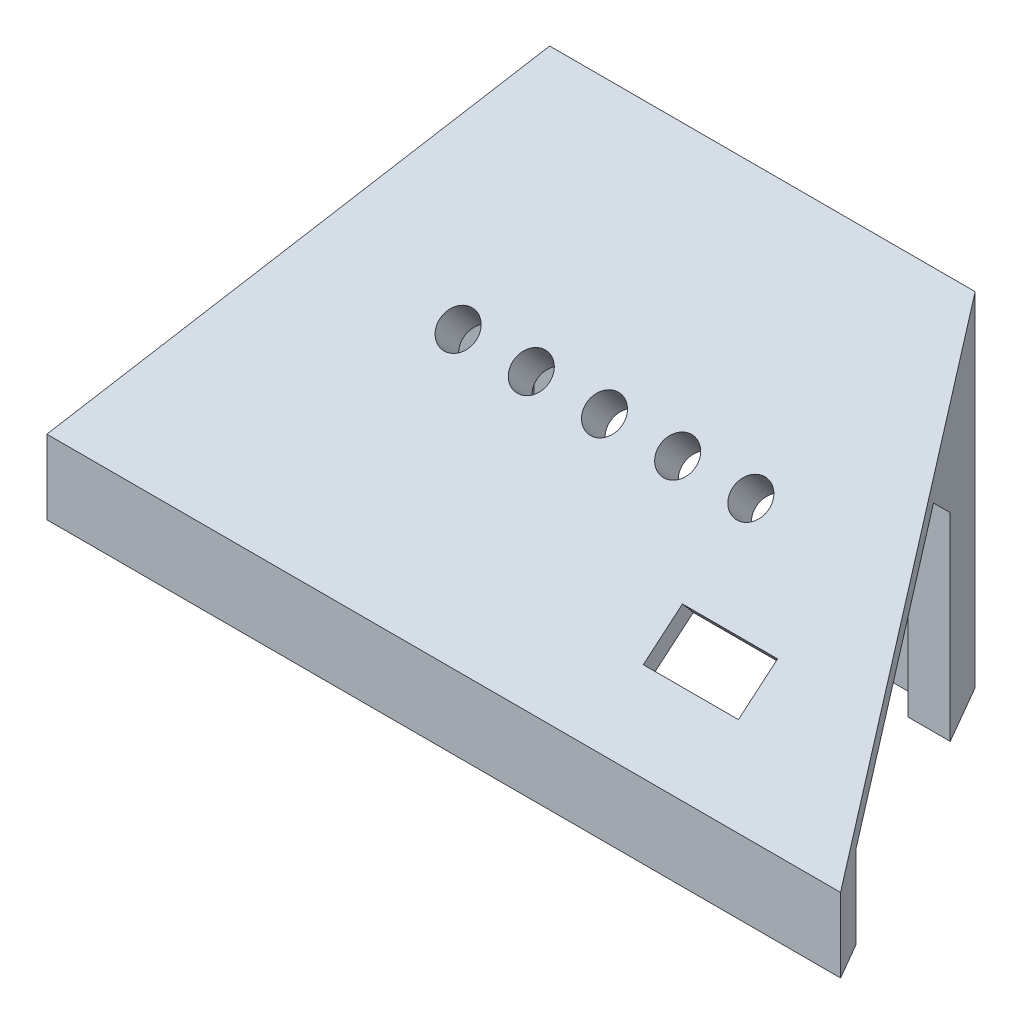
SolidWorks part; units mm, degrees
note: '?' marks a value the reader was unsure of.
other "Markup1"
sketch "Sketch17"
other "Markup2"
sketch "Sketch18"
ref_plane "Front Plane" through (0, 0, 0) normal (0, 0, 1) x (1, 0, 0)
ref_plane "Top Plane" through (0, 0, 0) normal (0, 1, 0) x (1, 0, 0)
ref_plane "Right Plane" through (0, 0, 0) normal (1, 0, 0) x (0, 0, -1)
sketch "Sketch1" plane through (0, 0, 0) normal (0, 1, 0) x (1, 0, 0)
  line L0 (0, 0) -> (108.46, 0)
  line L1 (54.23, 0) -> (54.23, 49.682) construction
  line L2 (25.16, 43.55) -> (83.3, 43.55)
  line L3 (0, 0) -> (25.16, 43.55)
  line L4 (83.3, 43.55) -> (108.46, 0)
  point P8 (54.23, 43.55)
  dimension "D1" = 108.46
  dimension "D2" = 58.14
  dimension "D3" = 43.55
extrude "Boss-Extrude1" add sketch "Sketch1" along normal blind 10.13
sketch "Sketch4" plane through (0, 10.13, 0) normal (0, 1, 0) x (1, 0, 0)
  line L4 (25.16, 43.55) -> (0, 0)
  line L5 (0, 0) -> (108.46, 0)
  line L6 (108.46, 0) -> (83.3, 43.55)
  line L7 (83.3, 43.55) -> (25.16, 43.55)
  line L8 (25.16, 43.55) -> (0, 0)
  line L9 (0, 0) -> (108.46, 0)
  line L10 (108.46, 0) -> (83.3, 43.55)
  line L11 (83.3, 43.55) -> (25.16, 43.55)
  dimension "D1" = 0
extrude "Boss-Extrude2" add sketch "Sketch4" along normal blind 36.74
chamfer "Chamfer1" distance 36.74 distance2 43.55 1 edges at (54.23, 46.87, 0)
sketch "Sketch10" plane through (0, 0, 0) normal (0, -1, 0) x (1, 0, 0)
  line L8 (8.6631, -5) -> (28.0458, -38.55)
  line L9 (28.0458, -38.55) -> (80.4142, -38.55)
  line L10 (80.4142, -38.55) -> (99.7969, -5)
  line L11 (99.7969, -5) -> (8.6631, -5)
  line L12 (8.6631, -5) -> (28.0458, -38.55)
  line L13 (28.0458, -38.55) -> (80.4142, -38.55)
  line L14 (80.4142, -38.55) -> (99.7969, -5)
  line L15 (99.7969, -5) -> (8.6631, -5)
  dimension "D1" = 5
extrude "Cut-Extrude1" cut sketch "Sketch10" against normal blind 50
sketch "Sketch11" plane through (0, 5.9181, 4.9926) normal (0, 0.7643, 0.6448) x (1, 0, 0)
  line L0 (8.6631, 13.0736) -> (99.7969, 13.0736) construction
  line L1 (99.7969, 13.0736) -> (80.4142, 56.9678) construction
  line L2 (80.4142, 56.9678) -> (28.0458, 56.9678) construction
  line L3 (28.0458, 56.9678) -> (8.6631, 13.0736) construction
  line L4 (8.6631, 13.0736) -> (99.7969, 13.0736)
  line L5 (99.7969, 13.0736) -> (80.4142, 56.9678)
  line L6 (80.4142, 56.9678) -> (28.0458, 56.9678)
  line L7 (28.0458, 56.9678) -> (8.6631, 13.0736)
ref_axis "Axis1" through (28.0458, 42.6519, -38.55) along (0, -1, 0)?
extrude "Boss-Extrude3" add sketch "Sketch11" along direction (0, -1, 0) on the side against the normal blind 3
sketch "Sketch12" plane through (0, 0, -43.55) normal (0, 0, -1) x (-1, 0, 0)
  line L0 (-83.3, 0) -> (-25.16, 0) construction
  line L1 (-32.36, 0) -> (-76.1, 0)
  line L2 (-32.36, 0) -> (-32.36, 39.6519)
  line L3 (-32.36, 39.6519) -> (-76.1, 39.6519)
  line L4 (-76.1, 0) -> (-76.1, 39.6519)
  line L5 (-25.16, 46.87) -> (-25.16, 0) construction
  line L6 (-83.3, 46.87) -> (-83.3, 0) construction
  line L7 (-80.4142, 39.6519) -> (-28.0458, 39.6519) construction
  dimension "D1" = 7.2
  dimension "D2" = 7.2
extrude "Cut-Extrude2" cut sketch "Sketch12" against normal up to vertex (5 mm away)
sketch "Sketch13" plane through (0, 5.9181, 4.9926) normal (0, 0.7643, 0.6448) x (1, 0, 0)
  line L0 (54.23, 63.5094) -> (54.23, 6.532) construction
  line L1 (83.3, 63.5094) -> (25.16, 63.5094) construction
  line L2 (108.46, 6.532) -> (0, 6.532) construction
  circle A0 centre (74.23, 35.2749) radius 2.5
  dimension "D1" = 5
  dimension "D2" = 20
extrude "Cut-Extrude3" cut sketch "Sketch13" against normal up to next
sketch "Sketch15" plane through (0, 5.9181, 4.9926) normal (0, 0.7643, 0.6448) x (1, 0, 0)
  circle A0 centre (74.23, 35.2749) radius 2.5 construction
  circle A1 centre (74.23, 35.2749) radius 2.5
  circle A2 centre (74.23, 35.2749) radius 3.5
  dimension "D1" = 1
extrude "Boss-Extrude4" add sketch "Sketch15" against normal blind 5
sketch "Sketch16" plane through (0, 5.9181, 4.9926) normal (0, 0.7643, 0.6448) x (1, 0, 0)
  line L5 (74.1954, 23.0907) -> (87.1954, 23.0907)
  line L6 (74.1954, 23.0907) -> (74.1954, 16.0907)
  line L7 (74.1954, 16.0907) -> (87.1954, 16.0907)
  line L8 (87.1954, 23.0907) -> (87.1954, 16.0907)
  point P1 (0, 0)
  point P6 (87.1954, 16.0907)
  point P11 (74.1954, 23.0907)
  point P14 (74.1954, 16.0907)
  dimension "D1" = 7
  dimension "D2" = 13
extrude "Cut-Extrude4" cut sketch "Sketch16" against normal up to next
ref_axis "Axis2" through (-5.3154, 10.13, 0) along (-1, 0, 0)?
pattern_linear "LPattern1" count 5 spacing 10 along (-1, 0, 0) of "Cut-Extrude3"
pattern_linear "LPattern2" count 5 spacing 10 along (-1, 0, 0) of "Boss-Extrude4"
sketch "Sketch20" plane through (0, 4.1654, 3.5141) normal (0, -0.7643, -0.6448) x (1, 0, 0)
  line L0 (10.5172, -11.1392) -> (2.0344, -11.1392)
  line L1 (8.6631, -11.1392) -> (99.7969, -11.1392) construction
  line L2 (0, -6.532) -> (25.16, -63.5094) construction
  line L3 (2.0344, -11.1392) -> (19.6508, -51.0334)
  line L4 (19.6508, -51.0334) -> (29.7598, -51.0334)
  line L5 (32.36, -55.0334) -> (76.1, -55.0334) construction
  line L6 (29.7598, -51.0334) -> (10.5172, -11.1392)
  line L7 (54.23, -11.1392) -> (54.23, -55.0334) construction
  line L8 (78.7002, -51.0334) -> (97.9428, -11.1392)
  line L9 (88.8092, -51.0334) -> (78.7002, -51.0334)
  line L10 (106.4256, -11.1392) -> (88.8092, -51.0334)
  line L11 (97.9428, -11.1392) -> (106.4256, -11.1392)
  point P16 (19.5092, -50.7126)
  point P17 (31.6141, -55.0334)
  point P18 (31.5604, -55.0334)
  point P19 (29.5745, -55.0334)
  point P20 (29.9502, -55.0334)
  point P21 (30.0039, -55.0334)
  point P22 (29.6818, -52.2867)
  dimension "D1" = 4
extrude "Cut-Extrude5" cut sketch "Sketch20" along direction (0, -1, 0) on the side of the normal up to next
chamfer "Chamfer2" distance 10 angle 45 2 edges at (85.0677, 37.0726, -35.4927) (23.3923, 37.0726, -35.4927)
chamfer "Chamfer3" distance 10 angle 45 2 edges at (76.1, 39.6519, -41.05) (32.36, 39.6519, -41.05)
